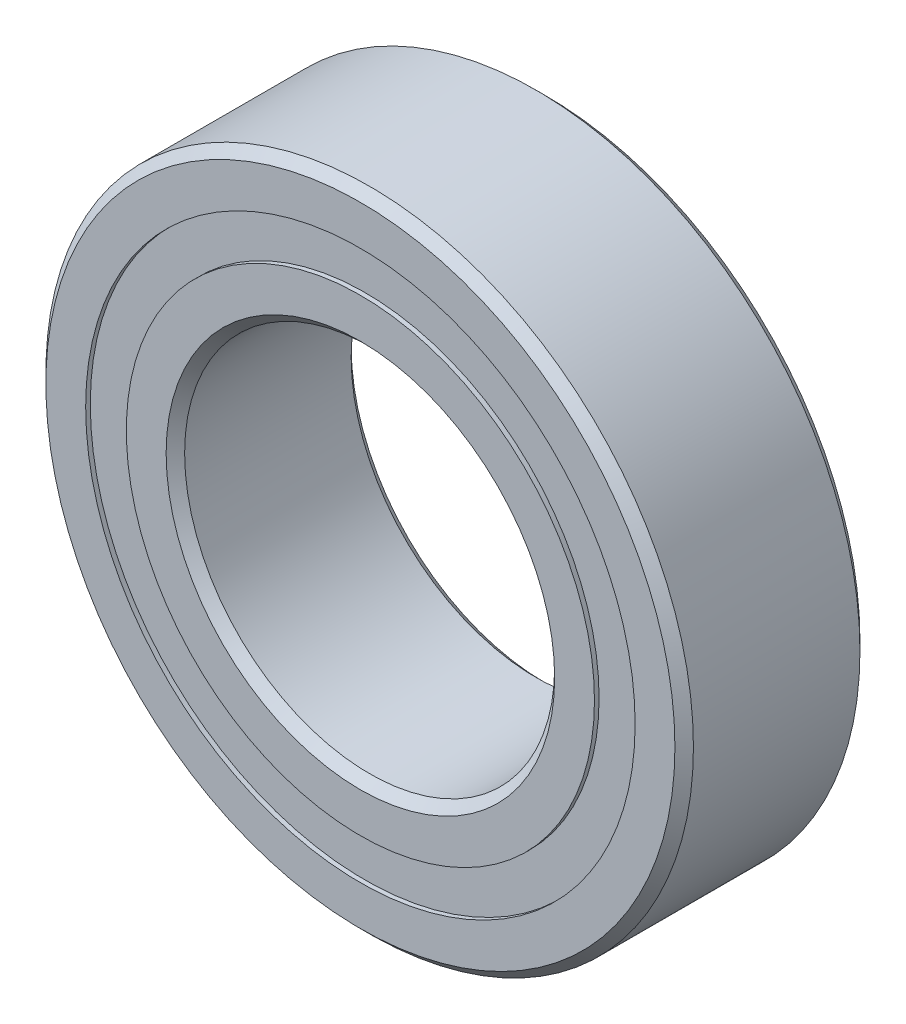
SolidWorks part; units mm, degrees
ref_plane "Front Plane" through (0, 0, 0) normal (0, 0, 1) x (1, 0, 0)
ref_plane "Top Plane" through (0, 0, 0) normal (0, 1, 0) x (1, 0, 0)
ref_plane "Right Plane" through (0, 0, 0) normal (1, 0, 0) x (0, 0, -1)
sketch "Sketch1" plane through (0, 0, 0) normal (1, 0, 0) x (0, 0, -1)
  line L0 (-2, 0) -> (2, 0) construction
  line L1 (0, 7) -> (0, -7) construction
  line L2 (1.8, 7) -> (-1.8, 7)
  line L3 (-1.8, 7) -> (-2, 6.8)
  line L4 (-2, 6.8) -> (-2, 5.9396)
  line L5 (-2, 5.9396) -> (-0.8889, 5.9396)
  line L6 (2, 5.9396) -> (0.8889, 5.9396)
  line L7 (2, 6.8) -> (2, 5.9396)
  line L8 (1.8, 7) -> (2, 6.8)
  line L9 (0, 7) -> (0, 5.5) construction
  line L10 (0, 5.5) -> (0, 4) construction
  arc A0 (-0.8889, 5.9396) -> (0.8889, 5.9396) centre (0, 5.5) cw
  point P14 (0, 4)
  dimension "D3" = 1.7778
  dimension "D1" = 45
  dimension "Width" = 4
  dimension "OD" = 14
  dimension "D2" = 0.2
  dimension "Shaft Dia" = 8
  dimension "D4" = 0.4396
revolve "Revolve1" add sketch "Sketch1" angle 360 about L0
sketch "Sketch3" plane through (0, 0, 0) normal (1, 0, 0) x (0, 0, -1)
  line L0 (-2, 5.0604) -> (-0.8889, 5.0604)
  line L1 (0, 7) -> (0, -7) construction
  line L2 (-2, 6.8) -> (-2, 5.9396) construction
  line L3 (-2, 5.0604) -> (-2, 4.2)
  line L4 (-1.8, 7) -> (-2, 6.8) construction
  line L5 (-2, 4.2) -> (-1.8, 4)
  line L6 (-1.8, 4) -> (1.8, 4)
  line L7 (1.8, 7) -> (1.8, -7) construction
  line L8 (1.8, 4) -> (2, 4.2)
  line L9 (2, -6.8) -> (2, 6.8) construction
  line L10 (2, 4.2) -> (2, 5.0604)
  line L11 (2, 5.0604) -> (0.8889, 5.0604)
  line L13 (1.8, 7) -> (2, 6.8) construction
  arc A0 (0.8889, 5.9396) -> (-0.8889, 5.9396) centre (0, 5.5) ccw construction
  arc A1 (0.8889, 5.0604) -> (-0.8889, 5.0604) centre (0, 5.5) cw
revolve "Revolve3" add sketch "Sketch3" angle 360 about L0
sketch "Sketch4" plane through (0, 0, 0) normal (1, 0, 0) x (0, 0, -1)
  line L0 (-0.9916, 5.5) -> (0.9916, 5.5)
  arc A2 (-0.9916, 5.5) -> (0.9916, 5.5) centre (0, 5.5) cw
  arc A3 (0.8889, 5.9396) -> (-0.8889, 5.9396) centre (0, 5.5) ccw construction
revolve "Revolve4" add sketch "Sketch4" angle 360 about L0
ref_axis "Axis1" through (0, 0, -2) along (0, 0, 1)
pattern_circular "CirPattern1" count 12 every 30 about axis through (0, 0, -2) along (0, 0, 1) of bodies 104
sketch "Sketch5" plane through (0, 0, 0) normal (1, 0, 0) x (0, 0, -1)
  line L0 (-2, 5.9396) -> (-0.8889, 5.9396) construction
  line L1 (-1.9, 5.9396) -> (-0.9916, 5.9396)
  line L2 (-1.9, 5.9396) -> (-1.9, 5.0604)
  line L3 (-1.9, 5.0604) -> (-0.9916, 5.0604)
  line L4 (-0.9916, 5.9396) -> (-0.9916, 5.0604)
  line L5 (-2, 5.0604) -> (-0.8889, 5.0604) construction
  line L6 (2, 5.9396) -> (0.8889, 5.9396) construction
  line L7 (1.9, 5.9396) -> (0.9916, 5.9396)
  line L8 (1.9, 5.9396) -> (1.9, 5.0604)
  line L9 (1.9, 5.0604) -> (0.9916, 5.0604)
  line L10 (0.9916, 5.9396) -> (0.9916, 5.0604)
  line L11 (2, 5.0604) -> (0.8889, 5.0604) construction
  line L12 (-1.8, 7) -> (-2, 6.8) construction
  point P18 (-1.9, 6.9)
revolve "Revolve5" add sketch "Sketch5" angle 360 about L0
sketch "Sketch6" plane through (0, 0, 0) normal (1, 0, 0) x (0, 0, -1)
  line L0 (2, 0) -> (-2, 0) construction
  line L1 (2, 5.9396) -> (0.9, 5.9396)
  line L2 (2, 5.9396) -> (2, 9.5)
  line L3 (2, 9.5) -> (0.9, 9.5)
  line L4 (0.9, 5.9396) -> (0.9, 9.5)
  dimension "Th" = 1.1
  dimension "Flange OD" = 19
revolve "Revolve6" [suppressed] add sketch "Sketch6" angle 360 about L0
equation "\"D2@Sketch1\" = \"Width@Sketch1\"*.05"
equation "\"D3@Sketch1\" = \"Width@Sketch1\"/2.25"
equation "\"D4@Sketch1\" = (((\"OD@Sketch1\"-\"Width@Sketch1\")/2)/3.25)/3.5"
equation "\"D2@CirPattern1\" = 360/\"Balls@CirPattern1\""
